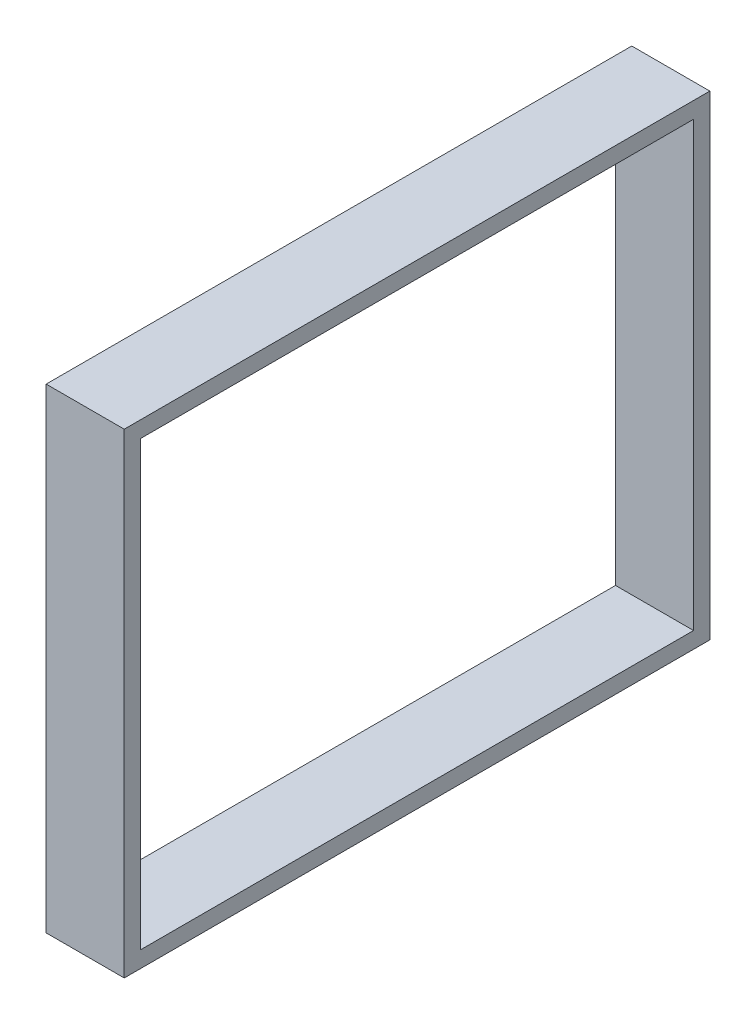
SolidWorks part; units mm, degrees
ref_plane "Front Plane" through (0, 0, 0) normal (0, 0, 1) x (1, 0, 0)
ref_plane "Top Plane" through (0, 0, 0) normal (0, 1, 0) x (1, 0, 0)
ref_plane "Right Plane" through (0, 0, 0) normal (1, 0, 0) x (0, 0, -1)
sketch "Tie Sketch" plane through (0, 0, 0) normal (1, 0, 0) x (0, 0, -1)
  line L0 (18, 67.55) -> (18, 96.77)
  line L1 (18, 96.77) -> (-18, 96.77)
  line L2 (-18, 96.77) -> (-18, 67.55)
  line L3 (-18, 67.55) -> (18, 67.55)
  line L4 (17, 68.55) -> (17, 95.77)
  line L5 (17, 95.77) -> (-17, 95.77)
  line L6 (-17, 95.77) -> (-17, 68.55)
  line L7 (-17, 68.55) -> (17, 68.55)
extrude "Tie" add sketch "Tie Sketch" along normal mid plane 4.8
ref_axis "Engine Axis" through (2.64, 0, 0) along (-1, 0, 0)
